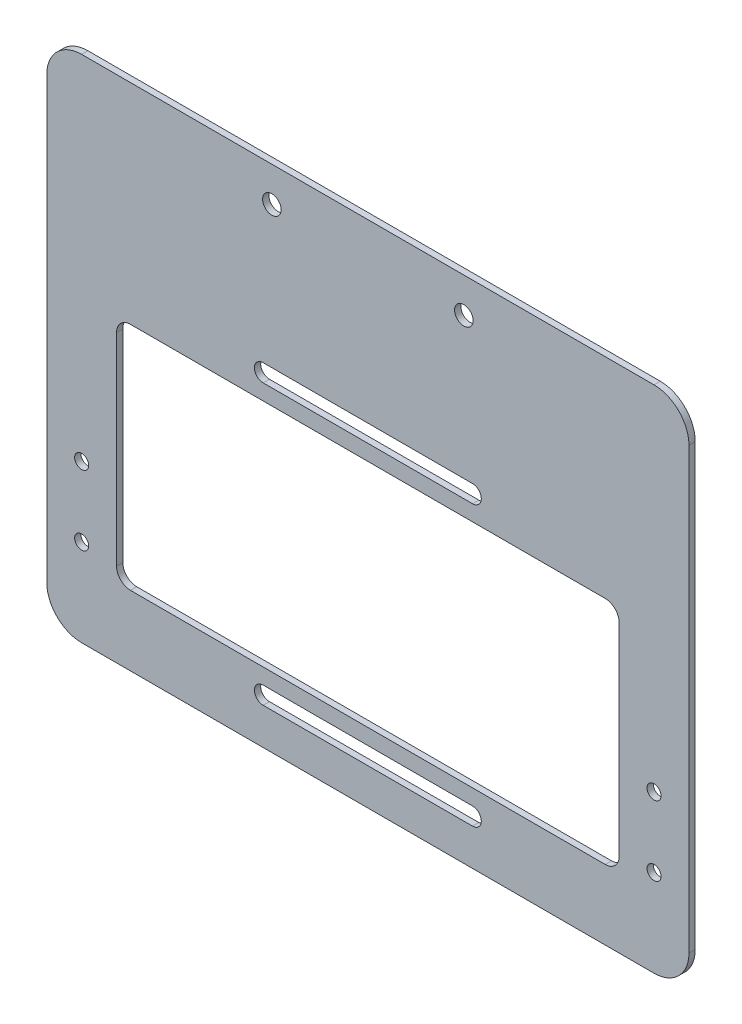
SolidWorks part; units mm, degrees
ref_plane "Front Plane" through (0, 0, 0) normal (0, 0, 1) x (1, 0, 0)
ref_plane "Top Plane" through (0, 0, 0) normal (0, 1, 0) x (1, 0, 0)
ref_plane "Right Plane" through (0, 0, 0) normal (1, 0, 0) x (0, 0, -1)
sketch "Sketch1" plane through (0, 0, 0) normal (0, 0, 1) x (1, 0, 0)
  line L1 (-116.84, 92.71) -> (116.84, 92.71)
  line L2 (-116.84, 92.71) -> (-116.84, -92.71)
  line L3 (-116.84, -92.71) -> (116.84, -92.71)
  line L4 (116.84, 92.71) -> (116.84, -92.71)
  line L5 (-116.84, 92.71) -> (116.84, -92.71) construction
  line L6 (-116.84, -92.71) -> (116.84, 92.71) construction
  line L7 (-86.36, 16.51) -> (86.36, 16.51)
  line L8 (-91.44, 11.43) -> (-91.44, -62.23)
  line L9 (-86.36, -67.31) -> (86.36, -67.31)
  line L10 (91.44, 11.43) -> (91.44, -62.23)
  line L11 (-91.44, 16.51) -> (91.44, -67.31) construction
  line L12 (-91.44, -67.31) -> (91.44, 16.51) construction
  arc A0 (86.36, -67.31) -> (91.44, -62.23) centre (86.36, -62.23) ccw
  arc A1 (86.36, 16.51) -> (91.44, 11.43) centre (86.36, 11.43) cw
  arc A2 (-91.44, 11.43) -> (-86.36, 16.51) centre (-86.36, 11.43) cw
  arc A3 (-86.36, -67.31) -> (-91.44, -62.23) centre (-86.36, -62.23) cw
  point P0 (0, 0)
  point P5 (0, -25.4)
  dimension "D7" = 5.08
  dimension "D1" = 25.4
  dimension "D2" = 185.42
  dimension "D3" = 182.88
  dimension "D4" = 83.82
  dimension "D5" = 25.4
  dimension "D6" = 233.68
extrude "Boss-Extrude1" add sketch "Sketch1" along normal blind 2.286
sketch "Sketch2" plane through (0, 0, 2.286) normal (0, 0, 1) x (1, 0, 0)
  line L0 (38.1, 25.4) -> (-38.1, 25.4) construction
  line L1 (38.1, 22.225) -> (-38.1, 22.225)
  line L2 (38.1, 28.575) -> (-38.1, 28.575)
  line L3 (-91.44, 11.43) -> (-91.44, -62.23) construction
  line L4 (-91.44, -25.4) -> (91.44, -25.4) construction
  line L5 (-91.44, 11.43) -> (-91.44, -62.23) construction
  line L6 (91.44, -62.23) -> (91.44, 11.43) construction
  line L7 (38.1, -76.2) -> (-38.1, -76.2) construction
  line L8 (38.1, -73.025) -> (-38.1, -73.025)
  line L9 (38.1, -79.375) -> (-38.1, -79.375)
  arc A0 (38.1, 22.225) -> (38.1, 28.575) centre (38.1, 25.4) ccw
  arc A1 (-38.1, 28.575) -> (-38.1, 22.225) centre (-38.1, 25.4) ccw
  arc A2 (38.1, -73.025) -> (38.1, -79.375) centre (38.1, -76.2) cw
  arc A3 (-38.1, -79.375) -> (-38.1, -73.025) centre (-38.1, -76.2) cw
  point P2 (0, 25.4)
  point P7 (-91.44, -25.4)
  point P19 (0, -76.2)
  dimension "D1" = 76.2
  dimension "D2" = 50.8
  dimension "D3" = 6.35
extrude "Cut-Extrude1" cut sketch "Sketch2" against normal through all
hole_wizard "1/4 Clearance Hole2" positions "Sketch8" profile "Sketch7" hole size "1/4" standard "ANSI Inch" end condition through all
sketch "Sketch8" plane through (0, 0, 2.286) normal (0, 0, 1) x (1, 0, 0)
  line L3 (-34.925, 80.01) -> (34.925, 80.01) construction
  line L5 (116.84, 92.71) -> (-116.84, 92.71) construction
  point P0 (-34.925, 80.01)
  point P2 (34.925, 80.01)
  point P17 (0, 80.01)
  dimension "D1" = 69.85
  dimension "D2" = 12.7
sketch "Sketch7" plane through (-34.925, 80.01, 2.286) normal (1, 0, 0) x (0, -1, 0)
  line L0 (0, 0) -> (0, 2.286)
  line L1 (0, 2.286) -> (3.3782, 2.286)
  line L2 (3.3782, 2.286) -> (3.3782, 0)
  line L5 (3.3782, 0) -> (0, 0)
  line L11 (0, -6.35) -> (0, 107.95) construction
  dimension "Thru Hole Dia." = 6.7564
  dimension "Thru Hole Depth" = 2.286
fillet "Fillet1" radius 12.7 4 edges at (-116.84, 92.71, 1.143) (116.84, 92.71, 1.143) (-116.84, -92.71, 1.143) (116.84, -92.71, 1.143)
sketch "Sketch9" plane through (0, 0, 2.286) normal (0, 0, 1) x (1, 0, 0)
  line L0 (-104.14, -92.71) -> (104.14, -92.71) construction
  line L1 (-116.84, 80.01) -> (-116.84, -80.01) construction
  line L2 (116.84, -80.01) -> (116.84, 80.01) construction
  circle A0 centre (-104.14, -60.96) radius 2.5527
  circle A1 centre (104.14, -60.96) radius 2.5527
  circle A2 centre (104.14, -35.56) radius 2.5527
  circle A3 centre (-104.14, -35.56) radius 2.5527
  dimension "D3" = 5.1054
  dimension "D1" = 25.4
  dimension "D2" = 25.4
  dimension "D4" = 31.75
  dimension "D5" = 12.7
  dimension "D6" = 12.7
  dimension "D7" = 31.75
extrude "Cut-Extrude2" cut sketch "Sketch9" against normal through all
